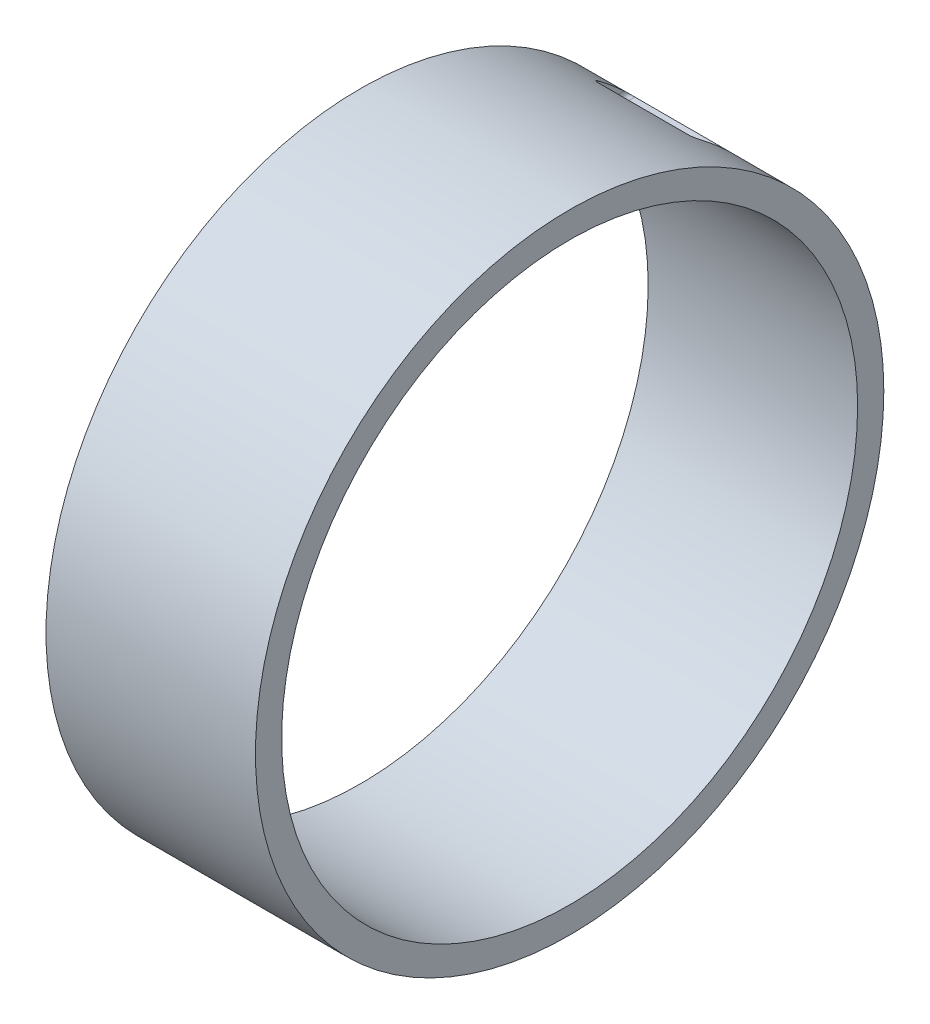
SolidWorks part; units mm, degrees
material "6061 Alloy"
ref_plane "Front Plane" through (0, 0, 0) normal (0, 0, 1) x (1, 0, 0)
ref_plane "Top Plane" through (0, 0, 0) normal (0, 1, 0) x (1, 0, 0)
ref_plane "Right Plane" through (0, 0, 0) normal (1, 0, 0) x (0, 0, -1)
sketch "Sketch1" plane through (0, 0, 0) normal (1, 0, 0) x (0, 0, -1)
  circle A0 centre (0, 0) radius 69.85
  circle A1 centre (0, 0) radius 76.2
  dimension "D1" = 6.35
  dimension "D2" = 139.7
extrude "Boss-Extrude1" add sketch "Sketch1" along normal mid plane 50.8
ref_plane "Plane1" through (6.35, 0, 0) normal (1, 0, 0) x (0, 0, -1)
ref_plane "Plane2" through (-6.35, 0, 0) normal (-1, 0, 0) x (0, 0, 1)
ref_axis "Axis1" through (25.4, 0, 0) along (-1, 0, 0)
sketch "Sketch4" plane through (0, 0, 0) normal (0, 0, 1) x (1, 0, 0)
  line L1 (-13.462, 61.976) -> (11.176, 61.976)
  line L2 (-13.462, 61.976) -> (-13.462, 54.356)
  line L3 (-13.462, 54.356) -> (11.176, 54.356)
  line L4 (11.176, 61.976) -> (11.176, 54.356)
  line L7 (25.4, -76.2) -> (25.4, 76.2) construction
  dimension "D1" = 24.638
  dimension "D2" = 14.224
  dimension "D3" = 7.62
extrude "Cut-Extrude1" cut sketch "Sketch4" against normal up to surface (44.333 mm away) up to face at (25.4, 0, -76.2)
fillet "Fillet1" radius 1.27 4 edges at (-13.462, 54.356, -48.6357) (-13.462, 61.976, -38.2755) (11.176, 61.976, -38.2755) (11.176, 54.356, -48.6357)
